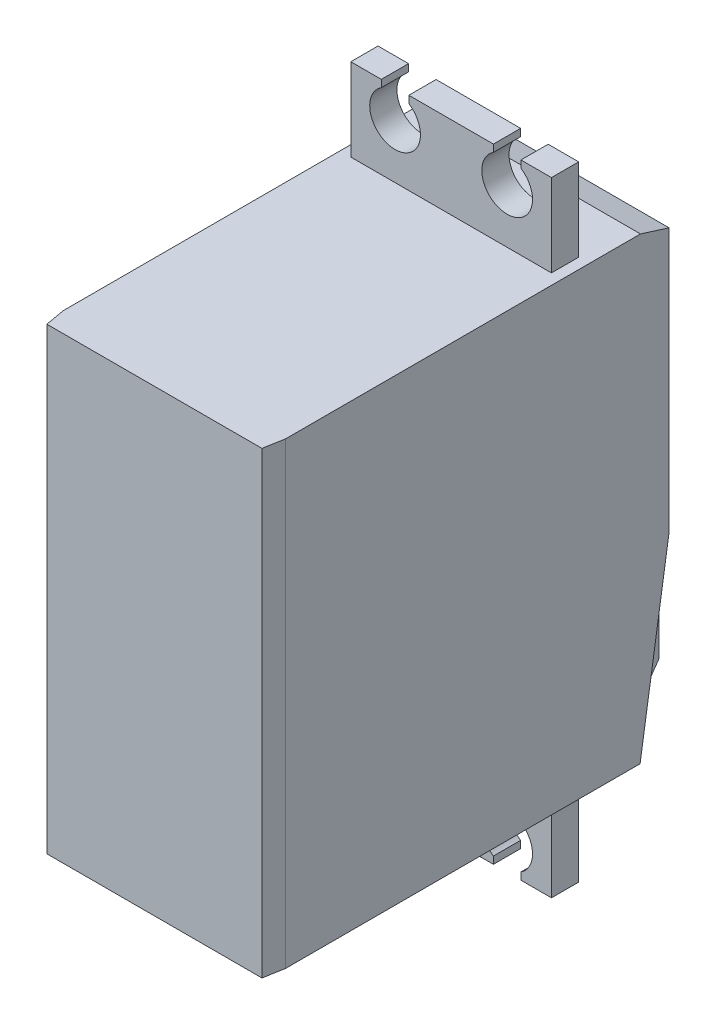
SolidWorks part; units mm, degrees
material "Servo Plastic"
ref_plane "Front Plane" through (0, 0, 0) normal (0, 0, 1) x (1, 0, 0)
ref_plane "Top Plane" through (0, 0, 0) normal (0, 1, 0) x (1, 0, 0)
ref_plane "Right Plane" through (0, 0, 0) normal (1, 0, 0) x (0, 0, -1)
sketch "Sketch1" plane through (0, 0, 0) normal (0, 0, 1) x (1, 0, 0)
  line L0 (0, 0) -> (0, 11.6439) construction
  line L1 (-9.8425, 20.32) -> (9.8425, 20.32)
  line L2 (-9.8425, 20.32) -> (-9.8425, -20.32)
  line L3 (-9.8425, -20.32) -> (9.8425, -20.32)
  line L4 (9.8425, 20.32) -> (9.8425, -20.32)
  line L5 (0, 0) -> (6.8718, 0) construction
  dimension "D1" = 40.64
  dimension "D2" = 19.685
extrude "Extrude1" add sketch "Sketch1" along normal blind 35.7632
chamfer "Chamfer1" distance 1.778 angle 10 1 edges at (9.8425, 0, 35.7632) first distance on face at (9.8425, 0, 17.8816)
chamfer "Chamfer2" distance 1.778 angle 10 1 edges at (-9.8425, 0, 35.7632) first distance on face at (-9.8425, 0, 17.8816)
chamfer "Chamfer3" distance 16.51 angle 8.85 1 edges at (0, -20.32, 0) first distance on face at (0, 0, 0)
sketch "Sketch2" plane through (0, 0, 0) normal (0, 0, -1) x (-1, 0, 0)
  line L0 (0, 0) -> (0, -14.6656) construction
  line L1 (-9.8425, 20.32) -> (9.8425, 20.32) construction
  line L2 (-8.9535, -2.54) -> (8.9535, -2.54)
  line L3 (-8.9535, -2.54) -> (-8.9535, -17.272)
  line L4 (-8.9535, -17.272) -> (8.9535, -17.272)
  line L5 (8.9535, -2.54) -> (8.9535, -17.272)
  dimension "D1" = 14.732
  dimension "D2" = 17.907
  dimension "D3" = 22.86
extrude "Extrude2" add sketch "Sketch2" against normal up to next
chamfer "Chamfer4" distance 3.302 angle 35 1 edges at (0, -17.272, 0) first distance on face at (0.1111, -1.143, 0)
sketch "Sketch3" plane through (0, 0, 0) normal (0, 0, -1) x (-1, 0, 0)
  line L0 (-9.8425, 20.32) -> (9.8425, 20.32) construction
  line L1 (0, 0) -> (0, -4.4447) construction
  line L2 (0, 0) -> (0, 9.4615) construction
  circle A0 centre (0, 9.4615) radius 7.1755
  dimension "D1" = 14.351
  dimension "D2" = 10.8585
extrude "Extrude3" add sketch "Sketch3" along normal blind 1.6256
chamfer "Chamfer5" distance 2.54 angle 17.5 1 edges at (0, 20.32, 0) first distance on face at (0, 20.32, 23.2495)
chamfer "Chamfer6" distance 1.6256 distance2 2.0955 1 edges at (-7.1755, 9.4615, -1.6256) first distance on face at (-7.1755, 9.4615, -1.6256)
sketch "Sketch4" plane through (0, 0, -1.6256) normal (0, 0, -1) x (-1, 0, 0)
  line L0 (0, 14.5415) -> (0, 4.3815) construction
  line L1 (-5.08, 9.4615) -> (5.08, 9.4615) construction
  circle A0 centre (0, 9.4615) radius 5.08 construction
  circle A1 centre (0, 9.4615) radius 2.9591
  dimension "D1" = 5.9182
extrude "Cut-Extrude1" cut sketch "Sketch4" against normal blind 10
sketch "Sketch5" plane through (0, 20.32, 0) normal (0, 1, 0) x (1, 0, 0)
  line L0 (0, -2.54) -> (0, -21.7911) construction
  line L1 (-8.89, -7.0612) -> (8.89, -7.0612)
  line L2 (-8.89, -7.0612) -> (-8.89, -9.4742)
  line L3 (-8.89, -9.4742) -> (8.89, -9.4742)
  line L4 (8.89, -7.0612) -> (8.89, -9.4742)
  line L5 (9.8425, -2.54) -> (-9.8425, -2.54) construction
  line L6 (9.529, -35.7632) -> (-9.529, -35.7632) construction
  dimension "D1" = 2.413
  dimension "D2" = 17.78
  dimension "D3" = 26.289
extrude "Extrude4" add sketch "Sketch5" along normal blind 7.3152
sketch "Sketch6" plane through (0, 0, 7.0612) normal (0, 0, -1) x (-1, 0, 0)
  line L0 (-9.8425, 20.32) -> (9.8425, 20.32) construction
  line L1 (-8.89, 27.6352) -> (-8.89, 20.32) construction
  line L2 (0, 27.6352) -> (0, 20.32) construction
  line L3 (-8.89, 27.6352) -> (8.89, 27.6352) construction
  line L4 (-4.9657, 25.1079) -> (-4.9657, 27.6352) construction
  line L5 (-6.1849, 27.6352) -> (-3.7465, 27.6352)
  line L6 (-6.1849, 27.6352) -> (-6.1849, 26.9964)
  line L7 (-8.89, 20.32) -> (8.89, 20.32) construction
  line L8 (-3.7465, 27.6352) -> (-3.7465, 26.9964)
  line L9 (4.9657, 25.1079) -> (4.9657, 27.6352) construction
  line L10 (3.7465, 27.6352) -> (6.1849, 27.6352)
  line L11 (3.7465, 27.6352) -> (3.7465, 26.9964)
  line L13 (6.1849, 27.6352) -> (6.1849, 26.9964)
  arc A0 (-6.1849, 26.9964) -> (-3.7465, 26.9964) centre (-4.9657, 25.1079) ccw
  arc A1 (3.7465, 26.9964) -> (6.1849, 26.9964) centre (4.9657, 25.1079) ccw
  dimension "D1" = 4.4958
  dimension "D4" = 9.9314
  dimension "D2" = 4.7879
  dimension "D3" = 3.9243
  dimension "D5" = 2.4384
extrude "Cut-Extrude2" cut sketch "Sketch6" against normal up to next
sketch "Sketch8" plane through (0, 0, 7.0612) normal (0, 0, -1) x (-1, 0, 0)
  line L0 (0, 20.32) -> (0, 27.6352) construction
  line L1 (-8.89, 20.32) -> (8.89, 20.32) construction
  line L2 (-3.7465, 27.6352) -> (3.7465, 27.6352) construction
  line L4 (-0.9525, 20.32) -> (0.9525, 20.32)
  line L5 (-0.9525, 20.32) -> (-0.9525, 24.13)
  line L6 (-0.9525, 24.13) -> (0.9525, 24.13)
  line L7 (0.9525, 20.32) -> (0.9525, 24.13)
  dimension "D1" = 1.905
  dimension "D2" = 3.81
extrude "Extrude5" add sketch "Sketch8" along normal blind 0.8636
ref_plane "Plane1" through (0, 0, 0) normal (0, 1, 0) x (-1, 0, 0)
mirror "Mirror1" about plane through (0, 0, 0) normal (0, 1, 0) of "Extrude5", "Cut-Extrude2", "Extrude4"
